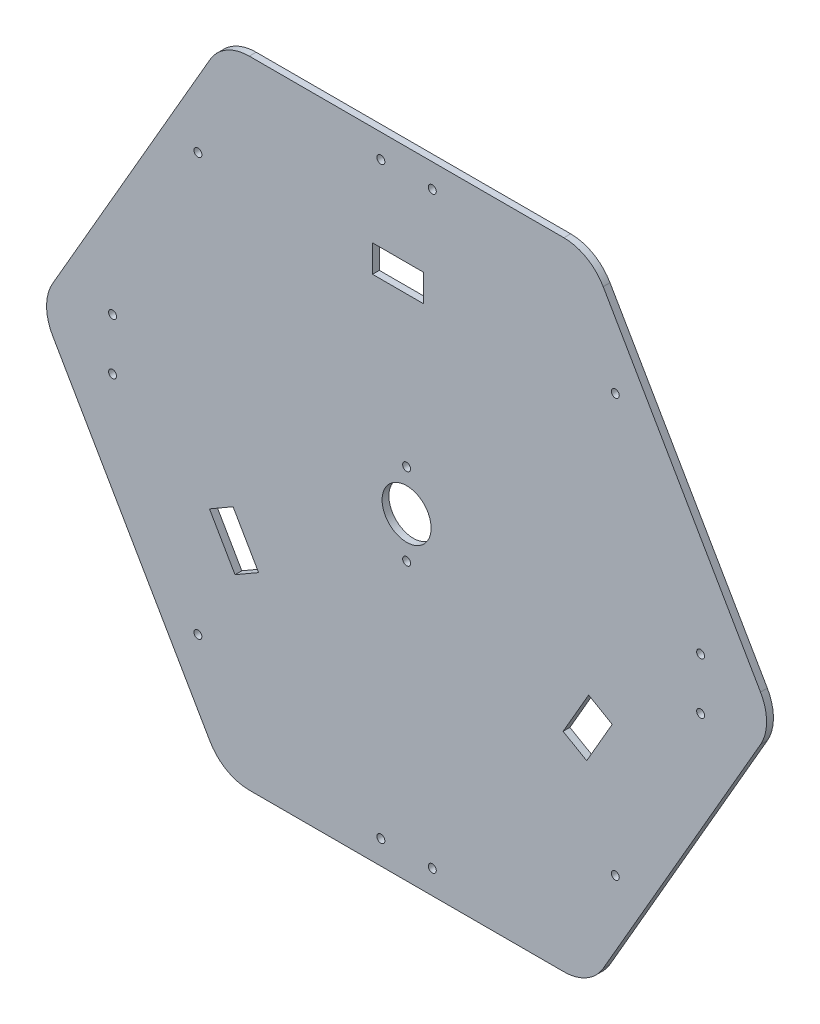
SolidWorks part; units mm, degrees
ref_plane "Alzado" through (0, 0, 0) normal (0, 0, 1) x (1, 0, 0)
ref_plane "Planta" through (0, 0, 0) normal (0, 1, 0) x (1, 0, 0)
ref_plane "Vista lateral" through (0, 0, 0) normal (1, 0, 0) x (0, 0, -1)
sketch "Croquis1" plane through (0, 0, 0) normal (0, 0, 1) x (1, 0, 0)
  line L0 (7.5, 95.9218) -> (-15, 83.9218) construction
  line L1 (-15, 95.9218) -> (7.5, 95.9218)
  line L2 (-15, 95.9218) -> (-15, 83.9218)
  line L3 (-15, 83.9218) -> (7.5, 83.9218)
  line L4 (7.5, 95.9218) -> (7.5, 83.9218)
  line L5 (-15, 95.9218) -> (7.5, 83.9218) construction
  line L6 (90.5708, -34.9705) -> (80.1784, -28.9705)
  line L7 (90.5708, -34.9705) -> (79.3208, -54.4561)
  line L8 (79.3208, -54.4561) -> (68.9284, -48.4561)
  line L9 (80.1784, -28.9705) -> (68.9284, -48.4561)
  line L10 (-75.5708, -60.9513) -> (-65.1784, -54.9513)
  line L11 (-75.5708, -60.9513) -> (-86.8208, -41.4657)
  line L12 (-86.8208, -41.4657) -> (-76.4284, -35.4657)
  line L13 (-65.1784, -54.9513) -> (-76.4284, -35.4657)
  line L14 (0, 0) -> (16.6639, 0) construction
  line L15 (0, 0) -> (0, 18) construction
  line L17 (-80.829, -140) -> (80.829, -140)
  line L18 (80.829, -140) -> (161.6581, 0)
  line L19 (161.6581, 0) -> (80.829, 140)
  line L20 (80.829, 140) -> (-80.829, 140)
  line L21 (-80.829, 140) -> (-161.6581, 0)
  line L22 (-161.6581, 0) -> (-80.829, -140)
  circle A0 centre (0, 0) radius 150
  circle A1 centre (0, 0) radius 10.8
  circle A2 centre (0, 0) radius 90 construction
  circle A3 centre (-3.75, 89.9218) radius 40 construction
  circle A4 centre (79.7496, -41.7133) radius 40 construction
  circle A5 centre (-75.9996, -48.2085) radius 40 construction
  circle A6 centre (0, 0) radius 18 construction
  circle A7 centre (0, 18) radius 1.75
  circle A8 centre (0, 0) radius 140 construction
  circle A11 centre (0, -18) radius 1.75
  point P11 (-3.75, 89.9218)
  point P18 (0, 0)
  point P28 (0, 0)
  point P39 (0, 0)
  point P46 (0, 140)
  dimension "D1" = 300
  dimension "D2" = 21.6
  dimension "D3" = 180
  dimension "D4" = 80
  dimension "D9" = 3.5
  dimension "D10" = 18
  dimension "D11" = 50
  dimension "D5" = 12
  dimension "D6" = 22.5
  dimension "D12" = 3.75
  dimension "D7" = 3
  dimension "D8" = 3
extrude "Saliente-Extruir1" add sketch "Croquis1" along normal blind 3 contours L19 A0 L20 L21 L22 L17 L18 A7 A1 L1 L4 L3 L2 L9 L6 L7 L8 L13 L10 L11 L12 | A0 L20 L21 | A0 L19 L20 | A0 L18 L19 | A0 L17 L18 | A0 L22 L17 | A0 L21 L22 region at (-76.7492, -132.9335, 0) region at (-72.9482, -126.3499, 0) region at (76.7492, -132.9335, 0) region at (-153.4984, 0, 0) region at (153.4984, 0, 0) region at (-76.7492, 132.9335, 0) region at (76.7492, 132.9335, 0)
fillet "Redondeo1" radius 20 6 edges at (80.829, 140, 1.5) (-80.829, 140, 1.5) (-161.6581, 0, 1.5) (-80.829, -140, 1.5) (80.829, -140, 1.5) (161.6581, 0, 1.5)
sketch "Croquis2" plane through (0, 0, 0) normal (0, 0, -1) x (-1, 0, 0)
  circle A0 centre (0, 0) radius 102.5 construction
  circle A1 centre (0, 0) radius 140 construction
  dimension "D1" = 280
  dimension "D2" = 205
sketch "Croquis3" plane through (0, 0, 0) normal (0, 0, -1) x (1, 0, 0)
  circle A0 centre (129.5053, 11.3302) radius 1.75
  circle A1 centre (91.9239, 91.9239) radius 1.75
  circle A2 centre (11.3302, 129.5053) radius 1.75
extrude "Cortar-Extruir1" cut sketch "Croquis3" against normal through all
pattern_circular "MatrizC1" count 4 over 360 about axis through (0, 0, 0) along (0, 0, 1) of "Cortar-Extruir1"
